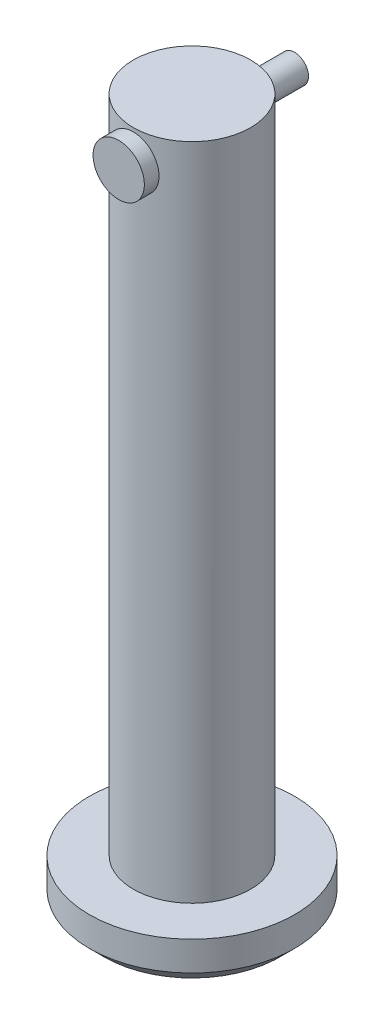
SolidWorks part; units mm, degrees
ref_plane "Front Plane" through (0, 0, 0) normal (0, 0, 1) x (1, 0, 0)
ref_plane "Top Plane" through (0, 0, 0) normal (0, 1, 0) x (1, 0, 0)
ref_plane "Right Plane" through (0, 0, 0) normal (1, 0, 0) x (0, 0, -1)
sketch "Sketch1" plane through (0, 0, 0) normal (0, 1, 0) x (1, 0, 0)
  circle A0 centre (0, 0) radius 4
extrude "Boss-Extrude1" add sketch "Sketch1" along normal blind 45
sketch "Sketch2" plane through (0, 0, 0) normal (0, -1, 0) x (1, 0, 0)
  circle A0 centre (0, 0) radius 7
  dimension "D1" = 14
extrude "Boss-Extrude2" add sketch "Sketch2" along normal blind 3
chamfer "Chamfer1" distance 1 angle 45 1 edges at (0, -3, -7)
sketch "Sketch3" plane through (0, 0, 0) normal (0, 0, 1) x (1, 0, 0)
  line L0 (4, 45) -> (-4, 45) construction
  circle A0 centre (0, 43) radius 1
  dimension "D1" = 2
  dimension "D2" = 2
extrude "Cut-Extrude1" cut sketch "Sketch3" against normal blind 10 and the other way blind 10
sketch "Sketch4" plane through (0, 0, 0) normal (0, 0, 1) x (1, 0, 0)
  circle A0 centre (0, 43) radius 0.95
  dimension "D1" = 1.9
extrude "Boss-Extrude3" add sketch "Sketch4" along normal blind 5 and the other way blind 7 separate body
sketch "Sketch5" plane through (0, 0, 5) normal (0, 0, 1) x (1, 0, 0)
  circle A0 centre (0, 43) radius 1.75
  dimension "D1" = 3.5
extrude "Boss-Extrude4" add sketch "Sketch5" against normal blind 1
